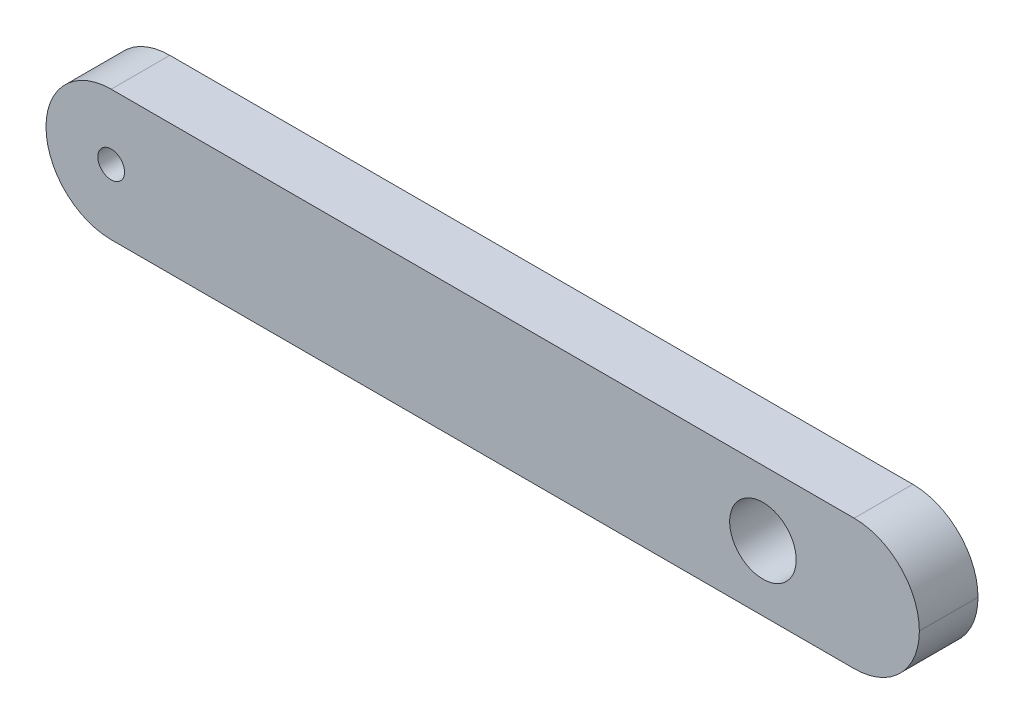
SolidWorks part; units mm, degrees
ref_plane "前视基准面" through (0, 0, 0) normal (0, 0, 1) x (1, 0, 0)
ref_plane "上视基准面" through (0, 0, 0) normal (0, 1, 0) x (1, 0, 0)
ref_plane "右视基准面" through (0, 0, 0) normal (1, 0, 0) x (0, 0, -1)
sketch "草图1" plane through (0, 0, 0) normal (0, 0, 1) x (1, 0, 0)
  line L1 (0, 0) -> (67, 0)
  line L2 (0, 0) -> (0, -10)
  line L3 (0, -10) -> (67, -10)
  line L4 (67, 0) -> (67, -10)
  circle A0 centre (5, -5) radius 1.025
  circle A1 centre (55, -5) radius 2.55
  dimension "D2" = 5.1
  dimension "D3" = 2.05
  dimension "D1" = 10
  dimension "D4" = 5
  dimension "D5" = 50
  dimension "D6" = 12
  dimension "D7" = 5
  dimension "D8" = 5
extrude "凸台-拉伸1" add sketch "草图1" along normal blind 4.5 contours A0 | L1 L4 L3 L2 | A1 region at (5, -5, 0)
fillet "圆角1" radius 5 4 edges at (0, -10, 2.25) (67, -10, 2.25) (67, 0, 2.25) (0, 0, 2.25)
